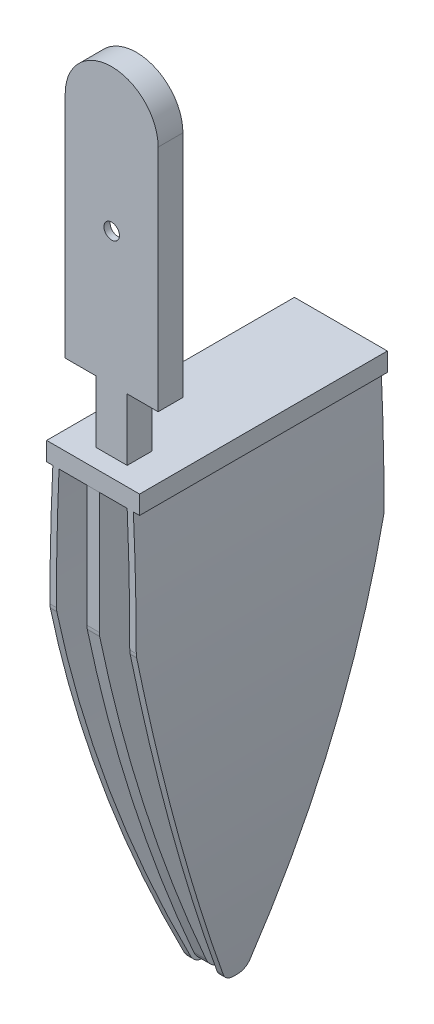
SolidWorks part; units mm, degrees
ref_plane "前基準面" through (0, 0, 0) normal (0, 0, 1) x (1, 0, 0)
ref_plane "上基準面" through (0, 0, 0) normal (0, 1, 0) x (1, 0, 0)
ref_plane "右基準面" through (0, 0, 0) normal (1, 0, 0) x (0, 0, -1)
sketch "草圖1" plane through (0, 0, 0) normal (0, 0, 1) x (1, 0, 0)
  line L0 (0, 0) -> (0, 4.6483) construction
  line L1 (7.5, 8) -> (7.5, 55)
  line L3 (-7.5, 8) -> (-7.5, 55)
  line L4 (-7.5, 8) -> (7.5, 8)
  line L5 (7.5, 4.6483) -> (-12.1697, 4.6483) construction
  arc A1 (7.5, 55) -> (-7.5, 55) centre (0, 55) ccw
  dimension "D1" = 47
extrude "填料-伸長1" add sketch "草圖1" along normal blind 2 and the other way blind 2
sketch "草圖3" plane through (0, 0, 0) normal (0, 0, 1) x (1, 0, 0)
  line L12 (0, -2.2) -> (0, 2.2) construction
  line L19 (-2.1062, 57.3548) -> (-4.9325, 40.3238)
  line L20 (2.1062, 57.3548) -> (4.9325, 40.3238)
  line L21 (2.1062, 21.6557) -> (4.9325, 38.6867)
  line L22 (-2.1062, 21.6557) -> (-4.9325, 38.6867)
  arc A9 (-4.9325, 40.3238) -> (-4.9325, 38.6867) centre (0, 39.5053) ccw
  arc A10 (2.1062, 57.3548) -> (-2.1062, 57.3548) centre (0, 57.0053) ccw
  arc A11 (2.1062, 21.6557) -> (-2.1062, 21.6557) centre (0, 22.0053) cw
  arc A12 (4.9325, 38.6867) -> (4.9325, 40.3238) centre (0, 39.5053) ccw
  dimension "D4" = 17.5
  dimension "D2" = 10
  dimension "D3" = 4.27
sketch "草圖6" plane through (0, 0, 0) normal (1, 0, 0) x (0, 0, -1)
  line L5 (-2, 8) -> (-5, 8)
  line L6 (-5, 8) -> (-5, 5)
  line L7 (-2, 8) -> (35, 8)
  line L9 (-2, 5) -> (35, 5)
  line L10 (35, 8) -> (35, 5)
  line L11 (-5, 5) -> (-2, 5)
  dimension "D1" = 3
  dimension "D2" = 3
extrude "填料-伸長2" add sketch "草圖6" along normal blind 7.5 and the other way blind 7.5
sketch "草圖8" plane through (0, 0, 0) normal (1, 0, 0) x (0, 0, -1)
  line L0 (35, 5) -> (35, -14.9)
  line L1 (-5, 5) -> (35, 5) construction
  line L3 (1, 5) -> (1, -0.7692) construction
  line L12 (1, 5) -> (35, 5)
  line L26 (35, 5) -> (35, -14.9047)
  line L28 (15, 5) -> (15, -75) construction
  line L30 (-5, 5) -> (-5, -14.9)
  line L31 (-5, 5) -> (35, 5)
  arc A9 (-5, -14.9) -> (15, -75) centre (261.0527, 40.2589) ccw
  arc A10 (35, -14.9) -> (15, -75) centre (-231.0527, 40.2589) cw
  dimension "D4" = 20
  dimension "D5" = 80
  dimension "D6" = 19.9
extrude "填料-伸長4" add sketch "草圖8" along normal blind 1 and the other way blind 1 separate body contours L0 A10 A9 L30 L31
sketch "草圖9" plane through (0, 0, 0) normal (1, 0, 0) x (0, 0, -1)
  line L0 (13.1021, 5.3065) -> (3.1021, 5.3065)
  line L1 (35.3755, -19.5858) -> (35.3755, -51.6928)
  line L2 (-1.8979, -16.6928) -> (-1.8979, -51.6928)
  arc A0 (35.3755, -51.6928) -> (25.3756, -64.9105) centre (17.6733, -48.6917) cw
  arc A1 (-1.8979, -51.6928) -> (8.102, -64.9105) centre (15.8043, -48.6917) ccw
  arc A2 (25.3756, -64.9105) -> (8.102, -64.9105) centre (16.7388, -64.9105) ccw
  arc A3 (13.1021, 5.3065) -> (35.3755, -19.5858) centre (-8.8884, -36.7816) cw
  arc A4 (3.1021, 5.3065) -> (-1.8979, -16.6928) centre (36.6834, -13.8937) ccw
ref_plane "平面5" through (0, 5, 0) normal (0, -1, 0) x (-1, 0, 0)
sketch "草圖14" plane through (0, 5, 0) normal (0, -1, 0) x (-1, 0, 0)
  line L0 (0, 1.0386) -> (9.1016, 1.0386) construction
  line L1 (0, 3.1021) -> (0, -1.9993) construction
  line L2 (0, 36.708) -> (0, -1.0851) construction
  line L3 (0, 22.9394) -> (0, -22.9394) construction
  line L4 (7.5, 35) -> (-7.5, 35) construction
  line L5 (-5.5, 1) -> (-6.5, 1)
  line L6 (-5.5, 1) -> (-5.5, 35)
  line L7 (-5.5, 35) -> (-6.5, 35)
  line L8 (-6.5, 1) -> (-6.5, 35)
  point P14 (0, 17.8114)
  dimension "D1" = 34
  dimension "D2" = 1
  dimension "D3" = 5.5
ref_plane "平面6" through (0, -71.5, 0) normal (0, -1, 0) x (-1, 0, 0)
ref_plane "平面10" through (0, 0, -18) normal (0, 0, 1) x (1, 0, 0)
sketch "草圖19" plane through (0, 0, -18) normal (0, 0, 1) x (1, 0, 0)
  line L0 (5.5, 5) -> (6.5, 5) construction
  line L1 (-8.25, 5) -> (8.25, 5) construction
  line L3 (-8.25, -71.5) -> (8.25, -71.5) construction
  line L5 (6.5, 5) -> (5.5, 5)
  line L6 (3, -71.5) -> (2, -71.5)
  line L9 (-3, -71.5) -> (-2, -71.5)
  line L10 (-6.5, 5) -> (-5.5, 5)
  arc A0 (5.5, 5) -> (2, -71.5) centre (-420, -13.8627) cw
  arc A1 (6.5, 5) -> (3, -71.5) centre (-403.5134, -14.5713) cw
  arc A2 (-6.5, 5) -> (-3, -71.5) centre (403.5134, -14.5713) ccw
  arc A3 (-5.5, 5) -> (-2, -71.5) centre (420, -13.8627) ccw
extrude "填料-伸長8" add sketch "草圖19" along normal blind 23 and the other way blind 17
sketch "草圖20" plane through (0, 0, 0) normal (1, 0, 0) x (0, 0, -1)
  line L9 (15, 28.6793) -> (15, -86.6932) construction
  line L14 (-5, -14.9) -> (-5, -71.5)
  line L18 (35, -14.9) -> (35, -75)
  line L19 (35, -75) -> (-5, -75)
  line L20 (-5, -14.9) -> (-5, -75)
  arc A7 (35, -14.9) -> (15, -75) centre (-231.0527, 40.2589) cw
  arc A8 (-5, -14.9) -> (15, -75) centre (261.0527, 40.2589) ccw
  point P14 (18, 5)
ref_plane "平面11" through (0, 0, 2) normal (0, 0, 1) x (1, 0, 0)
sketch "草圖21" plane through (0, 0, 2) normal (0, 0, 1) x (1, 0, 0)
  line L0 (-7.5, 55) -> (-7.5, 8) construction
  line L1 (-7.5, 8) -> (-2.5, 8)
  line L2 (-7.5, 8) -> (-7.5, 18)
  line L3 (-7.5, 18) -> (-2.5, 18)
  line L4 (-2.5, 8) -> (-2.5, 18)
  line L5 (0, 20.9814) -> (0, -1.1685) construction
  line L6 (7.5, 18) -> (2.5, 18)
  line L7 (2.5, 8) -> (2.5, 18)
  line L8 (7.5, 8) -> (2.5, 8)
  line L9 (7.5, 8) -> (7.5, 18)
  line L10 (-0.55, 5) -> (0.55, 5) construction
  dimension "D1" = 10
  dimension "D2" = 5
  dimension "D3" = 3
extrude "除料-伸長4" cut sketch "草圖21" against normal blind 4
ref_plane "平面12" through (0, 0, -2) normal (0, 0, -1) x (-1, 0, 0)
extrude "除料-伸長5" cut sketch "草圖3" against normal blind 2 and the other way blind 1
sketch "草圖23" plane through (0, 0, -2) normal (0, 0, -1) x (-1, 0, 0)
  line L0 (-5, 39.5053) -> (5, 39.5053) construction
  arc A0 (-4.9325, 40.3238) -> (-4.9325, 38.6867) centre (0, 39.5053) ccw construction
  arc A1 (4.9325, 38.6867) -> (4.9325, 40.3238) centre (0, 39.5053) ccw construction
  circle A2 centre (0, 39.5053) radius 1.25
  dimension "D1" = 2.5
extrude "除料-伸長6" cut sketch "草圖23" against normal blind 13
fillet "圓角11" radius 3 1 edges at (0, -75, -15) type face fillet first side face at (0, -45.2424, -4.1214) second side face at (0, -45.2424, -25.8786)
fillet "圓角12" radius 3 1 edges at (0, -14.9, 5) type face fillet first side face at (0, -4.95, 5) second side face at (0, -42.1477, -2.9193)
fillet "圓角13" radius 3 1 edges at (0, -14.9, -35) type face fillet first side face at (0, -4.95, -35) second side face at (0, -42.1477, -27.0807)
extrude "除料-伸長7" cut sketch "草圖20" against normal blind 10 and the other way blind 10 contours L18 A7 L19 | A8 L14 L20 L19 region at (0, -56.4312, -1.2729) region at (0, -56.4312, -28.7271)
fillet "圓角17" radius 2 1 edges at (2.5, -71.5, -16.6094) type face fillet first side face at (4.4646, -43.2, -25.8047) second side face at (2.5, -71.5, -15)
fillet "圓角18" radius 2 1 edges at (2.5, -71.5, -13.3906) type face fillet first side face at (4.4646, -43.2, -4.1953) second side face at (2.5, -71.5, -14.3525)
fillet "圓角19" radius 2 1 edges at (-2.5, -71.5, -16.6094) type face fillet first side face at (-4.4646, -43.2, -25.8047) second side face at (-2.5, -71.5, -15)
fillet "圓角20" radius 2 1 edges at (-2.5, -71.5, -13.3906) type face fillet first side face at (-2.5, -71.5, -14.3525) second side face at (-4.4646, -43.2, -4.1953)
fillet "圓角21" radius 3 1 edges at (-6.4417, -14.9, 5) type face fillet first side face at (0, -1.1325, 5) second side face at (-4.5462, -42.607, -3.9294)
fillet "圓角22" radius 3 1 edges at (6.4417, -14.9, 5) type face fillet first side face at (4.5462, -42.607, -3.9294) second side face at (0.0005, -1.081, 5)
fillet "圓角23" radius 3 1 edges at (-6.4417, -14.9, -35) type face fillet first side face at (0, -1.1325, -35) second side face at (-4.5462, -42.607, -26.0706)
fillet "圓角24" radius 3 1 edges at (6.4417, -14.9, -35) type face fillet first side face at (0.0005, -1.081, -35) second side face at (4.5462, -42.607, -26.0706)
